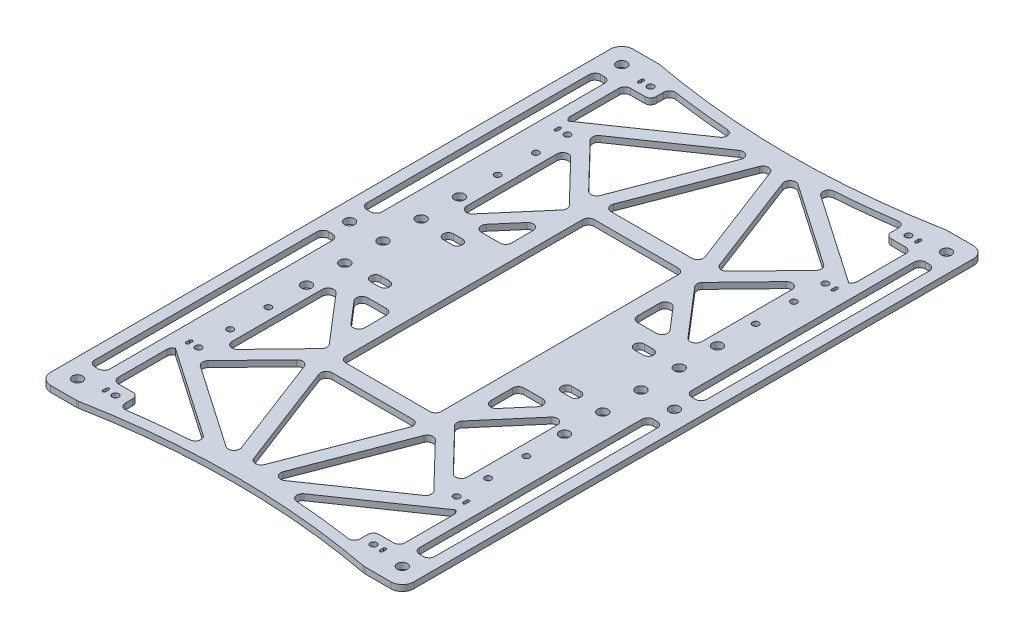
SolidWorks part; units mm, degrees
material "6061-O (SS)"
ref_plane "Front Plane" through (0, 0, 0) normal (0, 0, 1) x (1, 0, 0)
ref_plane "Top Plane" through (0, 0, 0) normal (0, 1, 0) x (1, 0, 0)
ref_plane "Right Plane" through (0, 0, 0) normal (1, 0, 0) x (0, 0, -1)
sketch "Sketch1" plane through (0, 0, 0) normal (0, 1, 0) x (1, 0, 0)
  line L1 (-95, 152.4) -> (95, 152.4)
  line L2 (-95, 152.4) -> (-95, -152.4)
  line L3 (-95, -152.4) -> (95, -152.4)
  line L4 (95, 152.4) -> (95, -152.4)
  line L5 (-95, 152.4) -> (95, -152.4) construction
  line L6 (-95, -152.4) -> (95, 152.4) construction
  point P0 (0, 0)
  dimension "D1" = 190
  dimension "D2" = 304.8
extrude "extrude rectangle" add sketch "Sketch1" along normal blind 3.175
sketch "Sketch2" plane through (0, 0, 0) normal (0, -1, 0) x (1, 0, 0)
  line L1 (-25, 65) -> (25, 65)
  line L2 (-25, 65) -> (-25, -65)
  line L3 (-25, -65) -> (25, -65)
  line L4 (25, 65) -> (25, -65)
  line L5 (-25, 65) -> (25, -65) construction
  line L6 (-25, -65) -> (25, 65) construction
  point P0 (0, 0)
  dimension "D1" = 50
  dimension "D2" = 130
extrude "wheel hole" cut sketch "Sketch2" against normal through all
sketch "Sketch3" plane through (0, 0, 0) normal (0, -1, 0) x (1, 0, 0)
  line L0 (0, 0) -> (-50, 0) construction
  line L1 (0, 0) -> (50, 0) construction
  line L2 (50, 0) -> (50, 19.05) construction
  line L7 (50, 0) -> (50, -19.05)
  line L8 (-50, 0) -> (-50, 19.05)
  line L13 (-50, 0) -> (-50, -19.05)
  dimension "D1" = 50
  dimension "D2" = 50
  dimension "D3" = 19.05
hole_wizard "M5 Clearance Slot2" positions "Sketch8" profile "Sketch9" size "M5" standard "ANSI Metric" slot yes end condition up to next
sketch "Sketch8" plane through (0, 0, 0) normal (0, -1, 0) x (-1, 0, 0)
  line L0 (45, -19.05) -> (55, -19.05) construction
  point P0 (50, -19.05)
  point P5 (50, 19.05)
  dimension "D1" = 10
sketch "Sketch9" plane through (-50, 0, 19.05) normal (1, 0, 0) x (0, 0, -1)
  line L0 (0, 0) -> (0, 3.176)
  line L1 (0, 3.176) -> (2.65, 3.176)
  line L2 (2.65, 3.176) -> (2.65, 0)
  line L5 (2.65, 0) -> (0, 0)
  line L11 (0, -6.35) -> (0, 107.95) construction
  dimension "Thru Hole Dia." = 5.3
  dimension "Thru Hole Depth" = 3.176
mirror "Mirror1" about plane through (0, 0, 0) normal (1, 0, 0) of "M5 Clearance Slot2"
sketch "Sketch12" plane through (0, 0, 0) normal (0, -1, 0) x (1, 0, 0)
  line L0 (85, 152.4) -> (85, -152.4) construction
  line L1 (-95, 152.4) -> (95, 152.4) construction
  line L2 (95, -152.4) -> (-95, -152.4) construction
  line L4 (95, 152.4) -> (95, -152.4) construction
  line L5 (81, 0) -> (0, 0) construction
  line L16 (0, 0) -> (0, -54.3033) construction
  line L20 (81, 10) -> (89, 10)
  line L21 (81, 10) -> (81, 132.4)
  line L22 (81, 132.4) -> (89, 132.4)
  line L23 (89, 10) -> (89, 132.4)
  line L24 (81, -10) -> (89, -10)
  line L25 (81, -10) -> (81, -132.4)
  line L26 (81, -132.4) -> (89, -132.4)
  line L27 (89, -10) -> (89, -132.4)
  circle A4 centre (85, -142.4) radius 2.65
  circle A5 centre (85, 142.4) radius 2.65
  circle A9 centre (85, 0) radius 2.65
  point P6 (85, 42.4)
  point P7 (85, 10.1257)
  point P10 (89, -10)
  point P11 (0, 0)
  point P18 (0, 0)
  point P21 (0, 0)
  point P22 (0, 0)
  point P29 (0, 0)
  dimension "D5" = 5.3
  dimension "D7" = 5.3
  dimension "D11" = 5.3
  dimension "D1" = 10
  dimension "D2" = 10
  dimension "D3" = 6
  dimension "D4" = 8
  dimension "D6" = 10
  dimension "D8" = 10
  dimension "D14" = 10
  dimension "D15" = 10
  dimension "D17" = 10
extrude "8020 stuff" cut sketch "Sketch12" against normal blind 10 contours A4 | A9 | A5 | L27 L24 L25 L26 | L20 L23 L22 L21 region at (85, 0, 71.2) region at (85, 0, -71.2) region at (85, 0, -142.4) region at (85, 0, 142.4) region at (85, 0, 0)
mirror "8020 stuff mirror" about plane through (0, 0, 0) normal (1, 0, 0) of "8020 stuff"
sketch "odrive" plane through (0, 0, 0) normal (0, -1, 0) x (1, 0, 0)
  line L0 (-95, 152.4) -> (95, 152.4) construction
  line L1 (-67.75, 140) -> (67.75, 140)
  line L2 (-67.75, 140) -> (-67.75, 96.5)
  line L3 (-67.75, 96.5) -> (67.75, 96.5)
  line L4 (67.75, 140) -> (67.75, 96.5)
  point P4 (0, 152.4)
  point P7 (0, 140)
  dimension "D1" = 135.5
  dimension "D2" = 43.5
  dimension "D3" = 12.4
sketch "Sketch22" plane through (0, 0, 0) normal (0, -1, 0) x (1, 0, 0)
  line L1 (67.5, -140) -> (-67.5, -140) construction
  line L2 (67.5, -140) -> (67.5, 140) construction
  line L3 (67.5, 140) -> (-67.5, 140) construction
  line L4 (-67.5, -140) -> (-67.5, 140) construction
  line L5 (67.5, -140) -> (-67.5, 140) construction
  line L6 (67.5, 140) -> (-67.5, -140) construction
  circle A0 centre (67.5, 140) radius 1.65
  circle A1 centre (67.5, 120) radius 1.65 construction
  circle A2 centre (67.5, 100) radius 1.65 construction
  circle A3 centre (67.5, 80) radius 1.65
  circle A4 centre (67.5, 60) radius 1.65
  circle A5 centre (67.5, 40) radius 1.65
  circle A6 centre (67.5, 20) radius 1.65
  circle A7 centre (67.5, 0) radius 1.65
  circle A8 centre (67.5, -20) radius 1.65
  circle A9 centre (67.5, -40) radius 1.65
  circle A10 centre (67.5, -60) radius 1.65
  circle A11 centre (67.5, -80) radius 1.65
  circle A12 centre (67.5, -100) radius 1.65 construction
  circle A13 centre (67.5, -120) radius 1.65 construction
  circle A14 centre (67.5, -140) radius 1.65
  circle A21 centre (-67.5, 140) radius 1.65
  circle A22 centre (-67.5, 120) radius 1.65 construction
  circle A23 centre (-67.5, 100) radius 1.65 construction
  circle A24 centre (-67.5, 80) radius 1.65
  circle A25 centre (-67.5, 60) radius 1.65
  circle A26 centre (-67.5, 40) radius 1.65
  circle A27 centre (-67.5, 20) radius 1.65
  circle A28 centre (-67.5, 0) radius 1.65
  circle A29 centre (-67.5, -20) radius 1.65
  circle A30 centre (-67.5, -40) radius 1.65
  circle A31 centre (-67.5, -60) radius 1.65
  circle A32 centre (-67.5, -80) radius 1.65
  circle A33 centre (-67.5, -100) radius 1.65 construction
  circle A34 centre (-67.5, -120) radius 1.65 construction
  circle A35 centre (-67.5, -140) radius 1.65
  point P0 (0, 0)
  point P1 (0, 0)
  point P6 (0, 0)
  dimension "D1" = 3.3
  dimension "D2" = 135
  dimension "D3" = 280
  dimension "D4" = 15
  dimension "D6" = 15
extrude "little holes??" cut sketch "Sketch22" against normal blind 10
sketch "Sketch27" plane through (0, 0, 0) normal (0, -1, 0) x (1, 0, 0)
  line L1 (0, 153.9852) -> (0, -152.4) construction
  line L2 (95, -152.4) -> (-95, -152.4) construction
  circle A0 centre (-67.5, 40) radius 2.65
  circle A1 centre (-67.5, 20) radius 2.65
  circle A2 centre (-67.5, 0) radius 2.65
  circle A3 centre (-67.5, -20) radius 2.65
  circle A4 centre (-67.5, -40) radius 2.65
  circle A5 centre (67.5, -40) radius 2.65
  circle A6 centre (67.5, -20) radius 2.65
  circle A7 centre (67.5, 0) radius 2.65
  circle A8 centre (67.5, 20) radius 2.65
  circle A9 centre (67.5, 40) radius 2.65
  dimension "D1" = 5.3
  dimension "D2" = 5
extrude "big holes??" cut sketch "Sketch27" against normal through all
sketch "Sketch28" plane through (0, 0, 0) normal (0, -1, 0) x (1, 0, 0)
  line L0 (-72.5, 140.9) -> (-72.5, 139.1) construction
  line L1 (-71.75, 140.9) -> (-71.75, 139.1)
  line L2 (-73.25, 140.9) -> (-73.25, 139.1)
  line L3 (-72.5, 97.4) -> (-72.5, 95.6) construction
  line L4 (-71.75, 97.4) -> (-71.75, 95.6)
  line L5 (-73.25, 97.4) -> (-73.25, 95.6)
  line L6 (0, 152.4) -> (0, -152.4) construction
  line L7 (-95, 152.4) -> (95, 152.4) construction
  line L8 (95, -152.4) -> (-95, -152.4) construction
  line L9 (72.5, 97.4) -> (72.5, 95.6) construction
  line L10 (71.75, 97.4) -> (71.75, 95.6)
  line L11 (73.25, 97.4) -> (73.25, 95.6)
  line L12 (72.5, 140.9) -> (72.5, 139.1) construction
  line L13 (71.75, 140.9) -> (71.75, 139.1)
  line L14 (73.25, 140.9) -> (73.25, 139.1)
  line L15 (-95, 0) -> (95, 0) construction
  line L16 (-95, -152.4) -> (-95, 152.4) construction
  line L17 (95, 152.4) -> (95, -152.4) construction
  line L18 (72.5, -140.9) -> (72.5, -139.1) construction
  line L19 (71.75, -140.9) -> (71.75, -139.1)
  line L20 (73.25, -140.9) -> (73.25, -139.1)
  line L21 (72.5, -97.4) -> (72.5, -95.6) construction
  line L22 (71.75, -97.4) -> (71.75, -95.6)
  line L23 (73.25, -97.4) -> (73.25, -95.6)
  line L24 (-72.5, -97.4) -> (-72.5, -95.6) construction
  line L25 (-71.75, -97.4) -> (-71.75, -95.6)
  line L26 (-73.25, -97.4) -> (-73.25, -95.6)
  line L27 (-72.5, -140.9) -> (-72.5, -139.1) construction
  line L28 (-71.75, -140.9) -> (-71.75, -139.1)
  line L29 (-73.25, -140.9) -> (-73.25, -139.1)
  line L30 (-72.5, 140) -> (-67.5, 140) construction
  line L31 (-72.5, 96.5) -> (-67.5, 96.5) construction
  line L32 (-72.5, 96.5) -> (-72.5, 140) construction
  arc A0 (-71.75, 140.9) -> (-73.25, 140.9) centre (-72.5, 140.9) ccw
  arc A1 (-73.25, 139.1) -> (-71.75, 139.1) centre (-72.5, 139.1) ccw
  circle A2 centre (-67.5, 140) radius 1.65 construction
  arc A3 (-71.75, 97.4) -> (-73.25, 97.4) centre (-72.5, 97.4) ccw
  arc A4 (-73.25, 95.6) -> (-71.75, 95.6) centre (-72.5, 95.6) ccw
  arc A5 (71.75, 97.4) -> (73.25, 97.4) centre (72.5, 97.4) cw
  arc A6 (73.25, 95.6) -> (71.75, 95.6) centre (72.5, 95.6) cw
  arc A7 (71.75, 140.9) -> (73.25, 140.9) centre (72.5, 140.9) cw
  arc A8 (73.25, 139.1) -> (71.75, 139.1) centre (72.5, 139.1) cw
  arc A9 (71.75, -140.9) -> (73.25, -140.9) centre (72.5, -140.9) ccw
  arc A10 (73.25, -139.1) -> (71.75, -139.1) centre (72.5, -139.1) ccw
  arc A11 (71.75, -97.4) -> (73.25, -97.4) centre (72.5, -97.4) ccw
  arc A12 (73.25, -95.6) -> (71.75, -95.6) centre (72.5, -95.6) ccw
  arc A13 (-71.75, -97.4) -> (-73.25, -97.4) centre (-72.5, -97.4) cw
  arc A14 (-73.25, -95.6) -> (-71.75, -95.6) centre (-72.5, -95.6) cw
  arc A15 (-71.75, -140.9) -> (-73.25, -140.9) centre (-72.5, -140.9) cw
  arc A16 (-73.25, -139.1) -> (-71.75, -139.1) centre (-72.5, -139.1) cw
  circle A17 centre (-67.5, 140) radius 1.65
  circle A18 centre (-67.5, 96.5) radius 1.65
  circle A21 centre (67.5, 96.5) radius 1.65
  circle A22 centre (67.5, 140) radius 1.65
  circle A23 centre (-67.5, -96.5) radius 1.65
  circle A24 centre (-67.5, -96.5) radius 1.65
  circle A25 centre (-67.5, -140) radius 1.65
  circle A26 centre (67.5, -140) radius 1.65
  circle A27 centre (67.5, -96.5) radius 1.65
  circle A28 centre (67.5, -96.5) radius 1.65
  circle A29 centre (-67.5, 53) radius 1.65 [skipped]
  point P2 (-72.5, 140)
  point P11 (-72.5, 96.5)
  point P24 (72.5, 96.5)
  point P31 (72.5, 140)
  point P44 (72.5, -140)
  point P51 (72.5, -96.5)
  point P58 (-72.5, -96.5)
  point P65 (-72.5, -140)
  point P74 (0, 0)
  point P75 (0, 0)
  dimension "D3" = 0.75
  dimension "D1" = 5
  dimension "D2" = 1.8
  dimension "D4" = 43.5
  dimension "D5" = 3
extrude "odrive holes" cut sketch "Sketch28" against normal through all contours L23 A12 L22 A11 | A27 | L20 A10 L19 A9 | A26 | A25 | A16 L29 A15 L28 | A14 L26 A13 L25 | A23 | A18 | L5 A4 L4 A3 | A17 | L2 A1 L1 A0 | A22 | A8 L14 A7 L13 | A21 | A6 L11 A5 L10 region at (-72.5, 0, 140) region at (-72.5, 0, 96.5) region at (72.5, 0, 96.5) region at (72.5, 0, 140) region at (72.5, 0, -140) region at (72.5, 0, -96.5) region at (-72.5, 0, -96.5) region at (-72.5, 0, -140) region at (-67.5, 0, 140) region at (-67.5, 0, 96.5) region at (67.5, 0, 96.5) region at (67.5, 0, 140) region at (-67.5, 0, -96.5) region at (-67.5, 0, -140) region at (67.5, 0, -140) region at (67.5, 0, -96.5)
sketch "Sketch29" plane through (0, 3.175, 0) normal (0, 1, 0) x (1, 0, 0)
  line L0 (25, -65) -> (-25, -65) construction
  line L1 (-61.5, -144.4) -> (61.5, -144.4) construction
  line L2 (-61.5, -144.4) -> (-61.5, -73)
  line L3 (-61.5, -73) -> (61.5, -73)
  line L4 (61.5, -144.4) -> (61.5, -73)
  line L5 (61.5, -73) -> (33, -73)
  line L6 (61.5, -73) -> (61.5, -29.7)
  line L7 (61.5, -29.7) -> (33, -29.7)
  line L8 (33, -73) -> (33, -29.7)
  line L9 (-61.5, -73) -> (-33, -73)
  line L10 (-61.5, -73) -> (-61.5, -29.7)
  line L11 (-61.5, -29.7) -> (-33, -29.7)
  line L12 (-33, -73) -> (-33, -29.7)
  line L13 (25, 65) -> (25, -65) construction
  line L14 (-25, -65) -> (-25, 65) construction
  line L15 (-95, -152.4) -> (95, -152.4) construction
  line L16 (-52.35, -21.7) -> (-47.65, -21.7) construction
  line L17 (47.65, -21.7) -> (52.35, -21.7) construction
  line L18 (-95, 152.4) -> (-95, -152.4) construction
  line L19 (-75, -102.5) -> (75, -102.5)
  line L20 (-75, -102.5) -> (-75, -134)
  line L21 (-75, -134) -> (75, -134)
  line L22 (75, -102.5) -> (75, -134)
  line L23 (95, -152.4) -> (95, 152.4) construction
  line L24 (-95, -152.4) -> (95, -152.4)
  circle A0 centre (67.5, -40) radius 2.65 construction
  circle A1 centre (-67.5, -40) radius 2.65 construction
  circle A2 centre (85, -142.4) radius 2.65 construction
  circle A4 centre (-67.5, -96.5) radius 1.65 construction
  circle A5 centre (67.5, -140) radius 1.65 construction
  arc A6 (-75, -152.4) -> (75, -152.4) centre (0, -545.3058) cw
  arc A7 (-61.5, -144.4) -> (61.5, -144.4) centre (0, -539.6439) cw
  circle A8 centre (-85, -142.4) radius 2.65 construction
  dimension "D5" = 6
  dimension "D10" = 10
  dimension "D15" = 400
  dimension "D1" = 8
  dimension "D2" = 8
  dimension "D3" = 8
  dimension "D4" = 8
  dimension "D6" = 6
  dimension "D7" = 8
  dimension "D8" = 8
  dimension "D9" = 10
  dimension "D11" = 6
  dimension "D12" = 6
  dimension "D13" = 20
  dimension "D14" = 20
extrude "hollowing" cut sketch "Sketch29" against normal blind 10 contours L3 L12 L11 L10 | L2 L19 L4 L3 | L2 L21 L4 L19 | L21 L2 L1 L4 | L22 L19 L4 L21 | L8 L3 L6 L7 | L20 L21 L2 L19 | A6 L24 region at (0, 3.175, 137.7516) region at (-68.25, 3.175, 118.25) region at (0, 3.175, 118.25) region at (0, 3.175, 87.75) region at (68.25, 3.175, 118.25) region at (-47.25, 3.175, 51.35) region at (47.25, 3.175, 51.35) region at (0, 3.175, 149.5602)
sketch "Sketch30" plane through (0, 3.175, 0) normal (0, 1, 0) x (1, 0, 0)
  line L0 (-33, -73) -> (-61.5, -102.5)
  line L1 (-61.5, -92.4253) -> (-33, -62.9253)
  line L2 (-61.5, -102.5) -> (-61.5, -29.7) construction
  line L3 (-33, -73) -> (-33, -29.7) construction
  line L4 (-61.5, -29.7) -> (-33, -62.9253)
  line L5 (-52.2776, -29.7) -> (-33, -52.1738)
  line L6 (-61.5, -29.7) -> (-33, -29.7) construction
  line L7 (-25.5049, -73) -> (0, -139.6439)
  line L8 (-33, -73) -> (33, -73) construction
  line L10 (-33, -73) -> (-7.4684, -139.7136)
  line L11 (-61.5, -102.5) -> (-7.4684, -139.7136)
  line L12 (-73.8409, -102.5) -> (-19.2384, -140.1068)
  line L13 (-75, -102.5) -> (-61.5, -102.5) construction
  line L14 (-75, -102.5) -> (-61.5, -102.5)
  line L15 (-61.5, -102.5) -> (-61.5, -29.7)
  line L17 (-33, -73) -> (33, -73)
  line L18 (-61.5, -29.7) -> (-33, -29.7)
  line L19 (-33, -73) -> (-33, -29.7)
  arc A0 (61.5, -144.4) -> (-61.5, -144.4) centre (0, -539.6439) ccw construction
  arc A1 (61.5, -144.4) -> (-61.5, -144.4) centre (0, -539.6439) ccw
  point P6 (0, -142.431)
  point P20 (-6.6318, -144.6787)
  point P21 (0, 0)
  dimension "D1" = 7
  dimension "D2" = 7
  dimension "D3" = 7
  dimension "D4" = 7
extrude "truss" add sketch "Sketch30" against normal up to surface (3.175 mm away) contours L4 L19 L5 L18 | L0 L19 L1 L15 | L17 L10 L7 | L12 L11 L14 region at (-16.4962, 3.175, 106.3336) region at (-47.25, 3.175, 82.7127) region at (-40.5425, 3.175, 121.1915) region at (-45.0927, 3.175, 43.7977) up to face at (0, 0, 49.6176)
mirror "truss mirror" about plane through (0, 0, 0) normal (1, 0, 0) of "truss"
mirror "hollowing/truss mirror" about plane through (0, 0, 0) normal (0, 0, 1) of "truss mirror", "truss", "hollowing"
fillet "inner fillet" radius 3 86 edges at (-33, 1.5875, 73) (-7.4684, 1.5875, 139.7136) (-61.5, 1.5875, 102.5) (-25, 1.5875, 65) (-25, 1.5875, -65) (25, 1.5875, -65) (25, 1.5875, 65) (-33, 1.5875, 29.7) (-33, 1.5875, 52.1738) (-52.2776, 1.5875, 29.7) (-61.5, 1.5875, 29.7) (-33, 1.5875, 62.9253) (-61.5, 1.5875, 92.4253) (33, 1.5875, 29.7) (52.2776, 1.5875, 29.7) (33, 1.5875, 52.1738) (-61.5, 1.5875, 134) (-75, 1.5875, 134) (-75, 1.5875, 102.5) (-73.8409, 1.5875, 102.5) (0, 1.5875, 139.6439) (-25.5049, 1.5875, 73) (25.5049, 1.5875, 73) (61.5, 1.5875, 29.7) (61.5, 1.5875, 92.4253) (33, 1.5875, 62.9253) (61.5, 1.5875, 102.5) (7.4684, 1.5875, 139.7136) (33, 1.5875, 73) (73.8409, 1.5875, 102.5) (75, 1.5875, 102.5) (75, 1.5875, 134) (61.5, 1.5875, 134) (-33, 1.5875, -29.7) (-52.2776, 1.5875, -29.7) (-33, 1.5875, -52.1738) (25.5049, 1.5875, -73) (-25.5049, 1.5875, -73) (0, 1.5875, -139.6439) (-61.5, 1.5875, -29.7) (-61.5, 1.5875, -92.4253) (-33, 1.5875, -62.9253) (-33, 1.5875, -73) (-61.5, 1.5875, -102.5) (-7.4684, 1.5875, -139.7136) (-73.8409, 1.5875, -102.5) (-75, 1.5875, -102.5) (-75, 1.5875, -134) (-61.5, 1.5875, -134) (33, 1.5875, -29.7) (33, 1.5875, -52.1738) (52.2776, 1.5875, -29.7) (61.5, 1.5875, -29.7) (33, 1.5875, -62.9253) (61.5, 1.5875, -92.4253) (61.5, 1.5875, -102.5) (33, 1.5875, -73) (7.4684, 1.5875, -139.7136) (61.5, 1.5875, -134) (75, 1.5875, -134) (75, 1.5875, -102.5) (73.8409, 1.5875, -102.5) (-19.2384, 1.5875, 140.1068) (61.5, 1.5875, 144.4) (19.2384, 1.5875, 140.1068) (-61.5, 1.5875, -144.4) (-19.2384, 1.5875, -140.1068) (61.5, 1.5875, -144.4) (19.2384, 1.5875, -140.1068) (-61.5, 1.5875, 144.4) (-81, 1.5875, -132.4) (-81, 1.5875, -10) (-89, 1.5875, -10) (-89, 1.5875, -132.4) (89, 1.5875, -10) (81, 1.5875, -10) (81, 1.5875, -132.4) (89, 1.5875, -132.4) (89, 1.5875, 132.4) (81, 1.5875, 132.4) (81, 1.5875, 10) (89, 1.5875, 10) (-81, 1.5875, 10) (-81, 1.5875, 132.4) (-89, 1.5875, 132.4) (-89, 1.5875, 10)
fillet "outer fillet" radius 6 8 edges at (75, 1.5875, -152.4) (95, 1.5875, -152.4) (95, 1.5875, 152.4) (75, 1.5875, 152.4) (-75, 1.5875, 152.4) (-95, 1.5875, -152.4) (-75, 1.5875, -152.4) (-95, 1.5875, 152.4)
